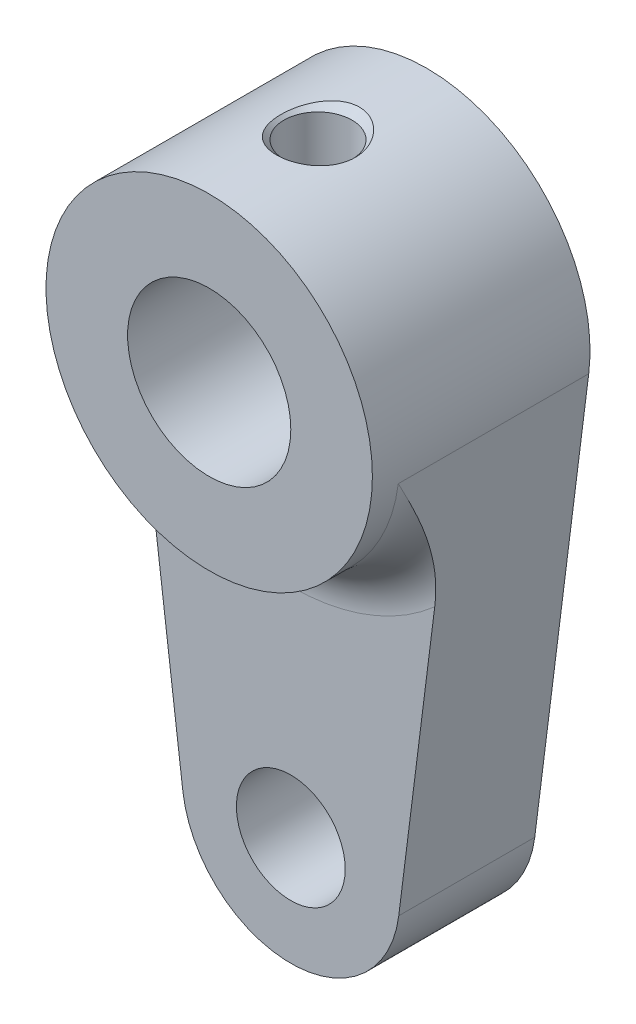
SolidWorks part; units mm, degrees
material "Alloy Steel (SS)"
ref_plane "Front Plane" through (0, 0, 0) normal (0, 0, 1) x (1, 0, 0)
ref_plane "Top Plane" through (0, 0, 0) normal (0, 1, 0) x (1, 0, 0)
ref_plane "Right Plane" through (0, 0, 0) normal (1, 0, 0) x (0, 0, -1)
sketch "Sketch1" plane through (0, 0, 0) normal (0, 0, 1) x (1, 0, 0)
  line L0 (-5.9529, -0.75) -> (-3.9686, -16.5)
  line L1 (5.9529, -0.75) -> (3.9686, -16.5)
  arc A0 (5.9529, -0.75) -> (-5.9529, -0.75) centre (0, 0) ccw
  arc A1 (-3.9686, -16.5) -> (3.9686, -16.5) centre (0, -16) ccw
  circle A2 centre (0, -16) radius 2
  dimension "D1" = 12
  dimension "D2" = 8
  dimension "D4" = 4
  dimension "D3" = 16
extrude "Boss-Extrude1" add sketch "Sketch1" along normal mid plane 5
sketch "Sketch2" plane through (0, 0, 2.5) normal (0, 0, 1) x (1, 0, 0)
  circle A0 centre (0, 0) radius 6
  dimension "D1" = 12
extrude "Boss-Extrude2" add sketch "Sketch2" along normal blind 3
sketch "Sketch3" plane through (0, 0, 5.5) normal (0, 0, 1) x (1, 0, 0)
  circle A0 centre (0, 0) radius 3
  dimension "D1" = 6
extrude "Cut-Extrude1" cut sketch "Sketch3" against normal through all
fillet "Fillet1" radius 2 1 edges at (0, -6, 2.5)
ref_plane "Plane1" through (0, 6, 0) normal (0, 1, 0) x (1, 0, 0)
hole_wizard "M3x0.5 Tapped Hole2" positions "Sketch8" profile "Sketch9" tap size "M3x0.5" standard "ANSI Metric"
sketch "Sketch8" plane through (0, 6, 0) normal (0, 1, 0) x (1, 0, 0)
  line L0 (6, 2.5) -> (-6, 2.5) construction
  point P0 (0, -1.5)
  dimension "D1" = 4
sketch "Sketch9" plane through (0, 6, 1.5) normal (1, 0, 0) x (0, 0, 1)
  line L0 (0, 0) -> (0, 7.7511)
  line L1 (0, 7.7511) -> (1.25, 7)
  line L2 (1.25, 7) -> (1.25, 0.275)
  line L3 (1.25, 0.275) -> (1.525, 0)
  line L5 (1.525, 0) -> (0, 0)
  line L6 (-1.25, 0.275) -> (-1.525, 0) construction
  line L10 (0, 7.7511) -> (-1.25, 7) construction
  line L11 (0, -6.35) -> (0, 107.95) construction
  dimension "Tap Drill Dia." = 2.5
  dimension "Tap Drill Depth" = 7
  dimension "Near C'Sink Dia." = 3.05
  dimension "Near C'Sink Angle" = 90
  dimension "Drill Angle" = 118
cosmetic thread "Hole Thread2" parameters "D1"=6, "D2"=3
